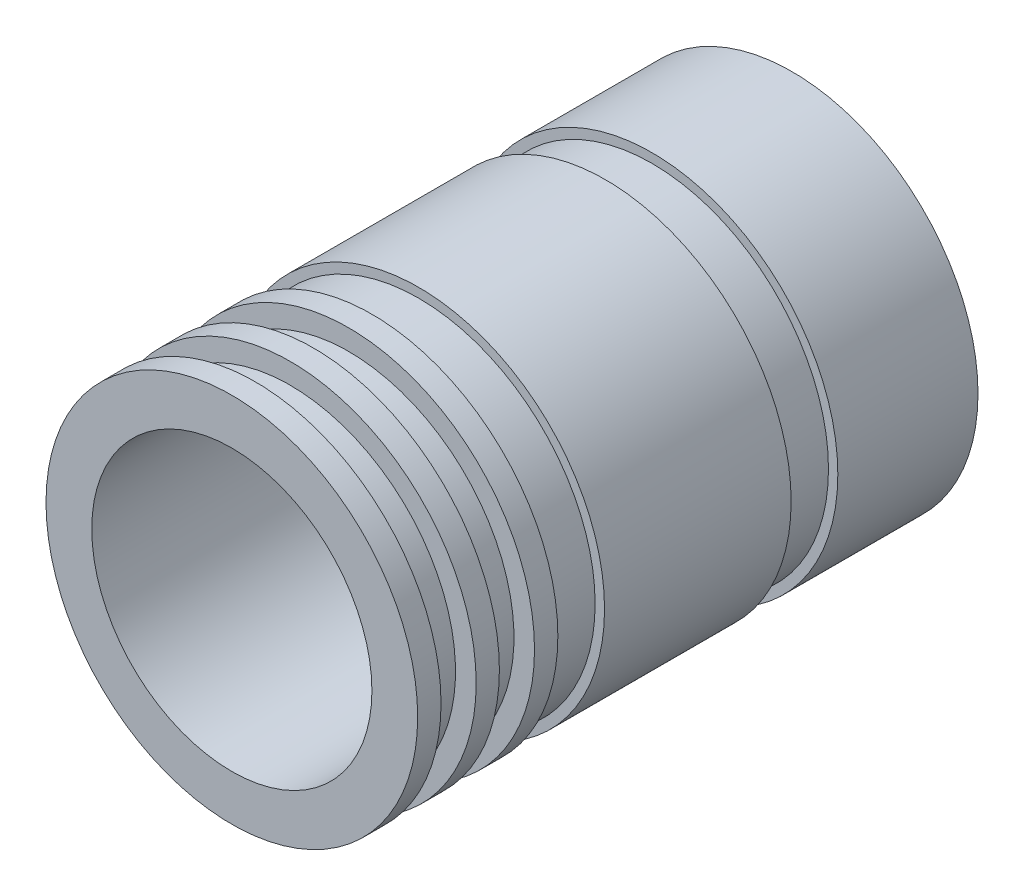
SolidWorks part; units mm, degrees
ref_plane "Front Plane" through (0, 0, 0) normal (0, 0, 1) x (1, 0, 0)
ref_plane "Top Plane" through (0, 0, 0) normal (0, 1, 0) x (1, 0, 0)
ref_plane "Right Plane" through (0, 0, 0) normal (1, 0, 0) x (0, 0, -1)
sketch "Sketch1" plane through (0, 0, 0) normal (0, 0, 1) x (1, 0, 0)
  circle A0 centre (0, 0) radius 25.273
  dimension "D1" = 50.546
extrude "Boss-Extrude1" add sketch "Sketch1" along normal blind 76.2
sketch "Sketch5" plane through (0, 0, 76.2) normal (0, 0, 1) x (1, 0, 0)
  circle A0 centre (0, 0) radius 19.05
  dimension "D1" = 38.1
extrude "Cut-Extrude2" cut sketch "Sketch5" against normal blind 76.2
ref_plane "Plane1" through (0, 0, 76.2) normal (-1, 0, 0) x (0, 1, 0)
ref_plane "Plane2" through (0, 0, 76.2) normal (-1, 0, 0) x (0, 1, 0)
ref_plane "Plane3" through (0, 0, 76.2) normal (-1, 0, 0) x (0, 1, 0)
ref_plane "Plane4" through (0, 0, 76.2) normal (-1, 0, 0) x (0, 1, 0)
sketch "Groove" plane through (0, 0, 0) normal (1, 0, 0) x (0, 0, -1)
  line L0 (0, 25.273) -> (-76.2, 25.273) construction
  line L1 (-76.2, 25.273) -> (-76.2, -25.273) construction
  line L2 (-73.025, 25.273) -> (-73.025, 22.479)
  line L3 (-73.025, 22.479) -> (-68.2625, 22.479)
  line L4 (-68.2625, 22.479) -> (-68.2447, 25.273)
  line L5 (-68.2447, 25.273) -> (-65.0875, 25.273)
  line L6 (-65.0875, 25.273) -> (-65.0875, 22.479)
  line L7 (-65.0875, 22.479) -> (-60.3123, 22.479)
  line L8 (-60.3123, 22.479) -> (-60.3123, 25.273)
  line L9 (-60.3123, 25.273) -> (-57.1373, 25.273)
  line L10 (-57.1373, 25.273) -> (-57.1373, 24.003)
  line L11 (-57.1373, 24.003) -> (-50.8, 24.003)
  line L12 (-50.8, 24.003) -> (-50.7873, 25.273)
  line L13 (-50.7873, 25.273) -> (-50.7873, 27.7239)
  line L14 (-50.7873, 27.7239) -> (-73.025, 27.7239)
  line L15 (-73.025, 27.7239) -> (-73.025, 25.273)
  line L16 (-38.1, 25.273) -> (-38.1, -25.3913) construction
  line L17 (-19.0627, 27.7239) -> (-25.4127, 27.7239)
  line L19 (-25.4127, 25.273) -> (-25.4127, 27.7239)
  line L20 (-25.4, 24.003) -> (-25.4127, 25.273)
  line L21 (-19.0627, 24.003) -> (-25.4, 24.003)
  line L22 (-19.0627, 25.273) -> (-19.0627, 24.003)
  line L31 (-19.0627, 25.273) -> (-19.0627, 27.7239)
  point P0 (-73.025, 25.273)
  point P1 (-68.2625, 25.273)
  point P4 (-68.2447, 25.273)
  point P5 (-65.0875, 25.273)
  point P7 (-60.3123, 25.273)
  point P9 (-57.1373, 25.273)
  point P10 (-50.7873, 25.273)
  point P11 (-50.8, 25.273)
  point P14 (-38.1, 25.273)
  point P27 (-38.1, -25.3913)
  point P44 (-25.4, 25.273)
  dimension "D1" = 3.175
  dimension "D2" = 4.7625
  dimension "D3" = 3.175
  dimension "D4" = 4.7752
  dimension "D5" = 3.175
  dimension "D6" = 2.794
  dimension "D7" = 25.4
  dimension "D8" = 2.794
  dimension "D9" = 1.27
ref_plane "Plane9" through (0, 0, 60.3123) normal (0, 0, 1) x (1, 0, 0)
sketch "groove path" plane through (0, 0, 60.3123) normal (0, 0, 1) x (1, 0, 0)
  circle A0 centre (0, 0) radius 25.273 construction
  circle A1 centre (0, 0) radius 25.273
sweep "Cut-Sweep4" cut profiles "Groove" path "groove path"
sketch "Sketch6" plane through (0, 0, 0) normal (1, 0, 0) x (0, 0, -1)
  line L1 (-3.1281, 0) -> (-41.2281, 0)
  line L3 (0, 25.273) -> (-19.0627, 25.273) construction
  line L10 (-3.1281, 21.844) -> (-7.9375, 21.844)
  line L11 (-7.9375, 21.844) -> (-7.9375, 18.034)
  line L12 (-7.9375, 18.034) -> (-36.4656, 18.034)
  line L13 (-36.4656, 18.034) -> (-36.4656, 21.8443)
  line L14 (-36.4656, 21.8443) -> (-41.2281, 21.8443)
  line L15 (-41.2281, 21.8443) -> (-41.2281, 0)
  line L17 (-3.1281, 0) -> (-3.1281, 21.844)
  point P4 (-7.8906, 25.273)
  point P5 (-3.1281, 25.273)
  point P6 (-11.0656, 25.273)
  point P9 (-15.8281, 25.273)
  dimension "D1" = 38.1
  dimension "D2" = 4.7625
  dimension "D3" = 3.175
  dimension "D4" = 4.7625
  dimension "D5" = 4.7625
  dimension "D6" = 3.429
  dimension "D8" = 3.81
ref_plane "Plane14" through (0, 0, 11.0656) normal (0, 0, -1) x (-1, 0, 0)
sketch "Sketch14" plane through (0, 0, 11.0656) normal (0, 0, -1) x (-1, 0, 0)
  circle A0 centre (0, 0) radius 19.05 construction
  circle A1 centre (0, 0) radius 19.05
sweep "Cut-Sweep5" cut profiles "Sketch6" path "Sketch14"
ref_plane "Plane15" through (0, 0, 38.1) normal (0, 0, 1) x (1, 0, 0)
sketch "Sketch15" plane through (0, 0, 38.1) normal (0, 0, 1) x (1, 0, 0)
  point P0 (0, 0)
